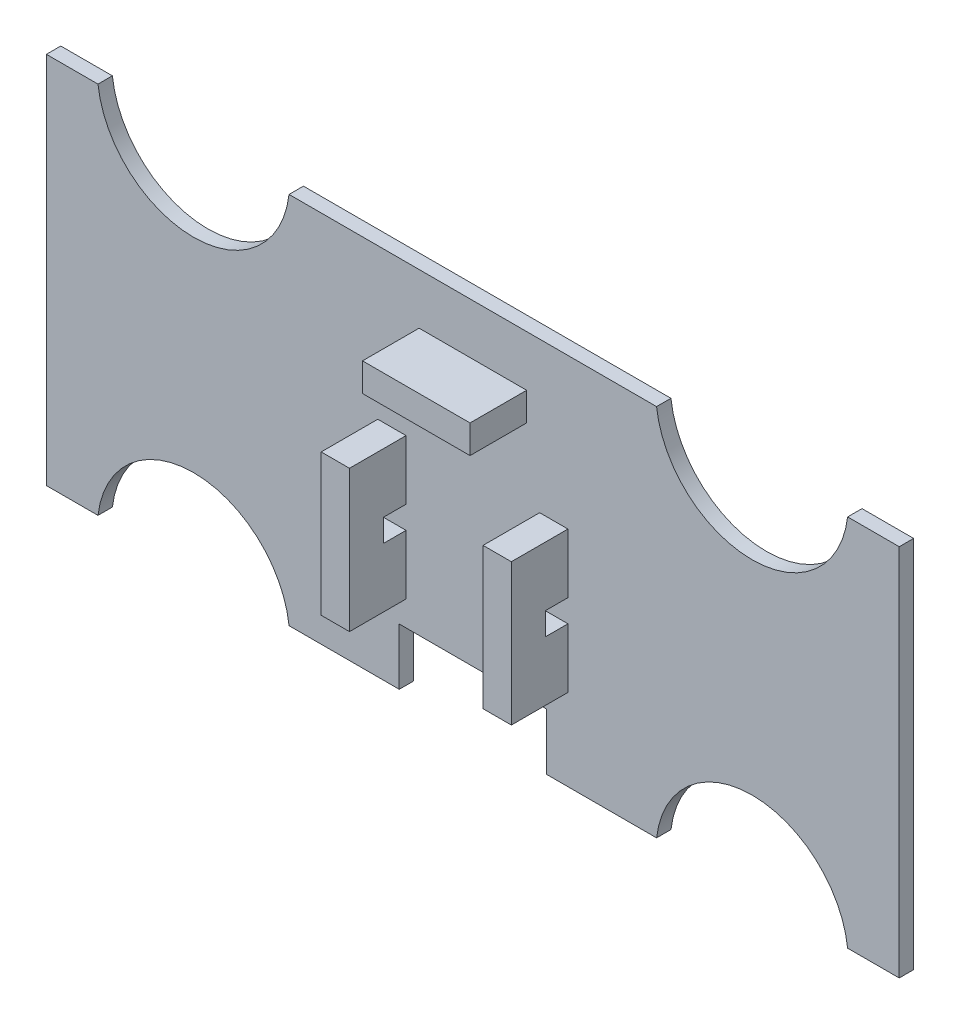
SolidWorks part; units mm, degrees
ref_plane "Front Plane" through (0, 0, 0) normal (0, 0, 1) x (1, 0, 0)
ref_plane "Top Plane" through (0, 0, 0) normal (0, 1, 0) x (1, 0, 0)
ref_plane "Right Plane" through (0, 0, 0) normal (1, 0, 0) x (0, 0, -1)
sketch "Sketch1" plane through (0, 0, 0) normal (0, 0, 1) x (1, 0, 0)
  line L0 (-32.4681, 33) -> (-13, 33)
  line L4 (13, 33) -> (32.4681, 33)
  line L5 (-66.2319, 33) -> (-75.35, 33)
  line L6 (-13, 33) -> (13, 33)
  line L7 (-75.35, -33) -> (-66.2319, -33)
  line L8 (-32.4681, -33) -> (-13, -33)
  line L9 (-13, -33) -> (13, -33)
  line L12 (13, -33) -> (32.4681, -33)
  line L13 (66.2319, 33) -> (75.35, 33)
  line L14 (-49.35, 18) -> (81.9561, 18) construction
  line L16 (75.35, 33) -> (75.35, -33)
  line L17 (75.35, -33) -> (66.2319, -33)
  line L51 (-75.35, 33) -> (-75.35, -33)
  arc A0 (-66.2319, 33) -> (-32.4681, 33) centre (-49.35, 35) ccw
  arc A3 (66.2319, -33) -> (32.4681, -33) centre (49.35, -35) ccw
  arc A4 (-32.4681, -33) -> (-66.2319, -33) centre (-49.35, -35) ccw
  arc A6 (32.4681, 33) -> (66.2319, 33) centre (49.35, 35) ccw
  dimension "D8" = 17
  dimension "D9" = 17
  dimension "D10" = 17
  dimension "D11" = 17
  dimension "D1" = 9.1181
  dimension "D2" = 9.1181
  dimension "D3" = 150.7
  dimension "D4" = 16.8819
  dimension "D5" = 16.8819
  dimension "D6" = 16.8819
  dimension "D7" = 16.8819
extrude "Boss-Extrude1" add sketch "Sketch1" along normal blind 2.54
sketch "Sketch2" plane through (0, 0, 2.54) normal (0, 0, 1) x (1, 0, 0)
  line L0 (-13, -33) -> (32.4681, -33) construction
  line L1 (-13, -33) -> (13.0161, -33)
  line L2 (-13, -33) -> (-13, -23)
  line L3 (-13, -23) -> (13.0161, -23)
  line L4 (13.0161, -33) -> (13.0161, -23)
  dimension "D1" = 10
  dimension "D2" = 19.4681
  dimension "D3" = 19.452
extrude "Cut-Extrude1" cut sketch "Sketch2" against normal blind 2.54
sketch "Sketch6" plane through (0, 0, 2.54) normal (0, 0, 1) x (1, 0, 0)
  line L0 (13.0161, -33) -> (32.4681, -33) construction
  line L1 (-11.79, -33) -> (11.81, -33)
  line L2 (-11.79, -33) -> (-11.79, 19.02)
  line L3 (-11.79, 19.02) -> (11.81, 19.02)
  line L4 (11.81, -33) -> (11.81, 19.02)
  line L5 (-11.79, -33) -> (11.81, 19.02) construction
  line L6 (-11.79, 19.02) -> (11.81, -33) construction
  line L8 (-13, -23) -> (-13, -33) construction
  line L11 (-11.79, 6.4332) -> (-16.79, 6.4332)
  line L12 (-11.79, 6.4332) -> (-11.79, -18.5668)
  line L13 (-11.79, -18.5668) -> (-16.79, -18.5668)
  line L14 (-16.79, 6.4332) -> (-16.79, -18.5668)
  line L15 (11.81, 6.4332) -> (16.81, 6.4332)
  line L16 (11.81, 6.4332) -> (11.81, -18.5668)
  line L17 (11.81, -18.5668) -> (16.81, -18.5668)
  line L18 (16.81, 6.4332) -> (16.81, -18.5668)
  line L19 (-9.49, 19.02) -> (9.51, 19.02)
  line L20 (-9.49, 19.02) -> (-9.49, 24.02)
  line L21 (-9.49, 24.02) -> (9.51, 24.02)
  line L22 (9.51, 19.02) -> (9.51, 24.02)
  point P0 (0.01, -6.99)
  dimension "D1" = 0
  dimension "D2" = 23.6
  dimension "D3" = 1.21
  dimension "D4" = 52.02
  dimension "D5" = 5
  dimension "D6" = 5
  dimension "D7" = 25
  dimension "D8" = 25
  dimension "D9" = 5
  dimension "D10" = 19
  dimension "D11" = 2.3
extrude "Boss-Extrude2" add sketch "Sketch6" along normal blind 10 contours L14 L13 L12 L11
extrude "Boss-Extrude3" add sketch "Sketch6<3>" along normal blind 10 contours L21 L22 L19 L20
sketch "Sketch6<3>" plane through (0, 0, 2.54) normal (0, 0, 1) x (1, 0, 0) same geometry as "Sketch6"
extrude "Boss-Extrude4" add sketch "Sketch6<4>" along normal blind 10 contours L18 L17 L16 L15
sketch "Sketch6<4>" plane through (0, 0, 2.54) normal (0, 0, 1) x (1, 0, 0) same geometry as "Sketch6"
sketch "Sketch9" plane through (-16.79, 0, 0) normal (-1, 0, 0) x (0, 0, 1)
  line L0 (2.54, 6.4332) -> (2.54, -18.5668) construction
  line L1 (6.54, -8.0668) -> (2.54, -8.0668)
  line L2 (6.54, -8.0668) -> (6.54, -4.0668)
  line L3 (6.54, -4.0668) -> (2.54, -4.0668)
  line L5 (6.54, -8.0668) -> (2.54, -5.3371) construction
  line L6 (6.54, -4.0668) -> (2.54, -5.3371) construction
  line L8 (2.54, -4.0668) -> (2.54, -8.0668)
  line L9 (12.54, -6.0668) -> (2.54, -6.0668)
  line L10 (12.54, 6.4332) -> (12.54, -18.5668) construction
  point P0 (2.54, -5.3371)
  line M7 (2.54, 6.4332) -> (2.54, -18.5668)
  dimension "D1" = 4
  dimension "D2" = 0
  dimension "D3" = 4
  dimension "D4" = 2
extrude "Cut-Extrude3" cut sketch "Sketch9" against normal through all contours L9 L2 L3 M7 | L2 L9 L8 L1 region at (-16.79, -7.0668, 4.54) region at (-16.79, -5.0668, 4.54)
